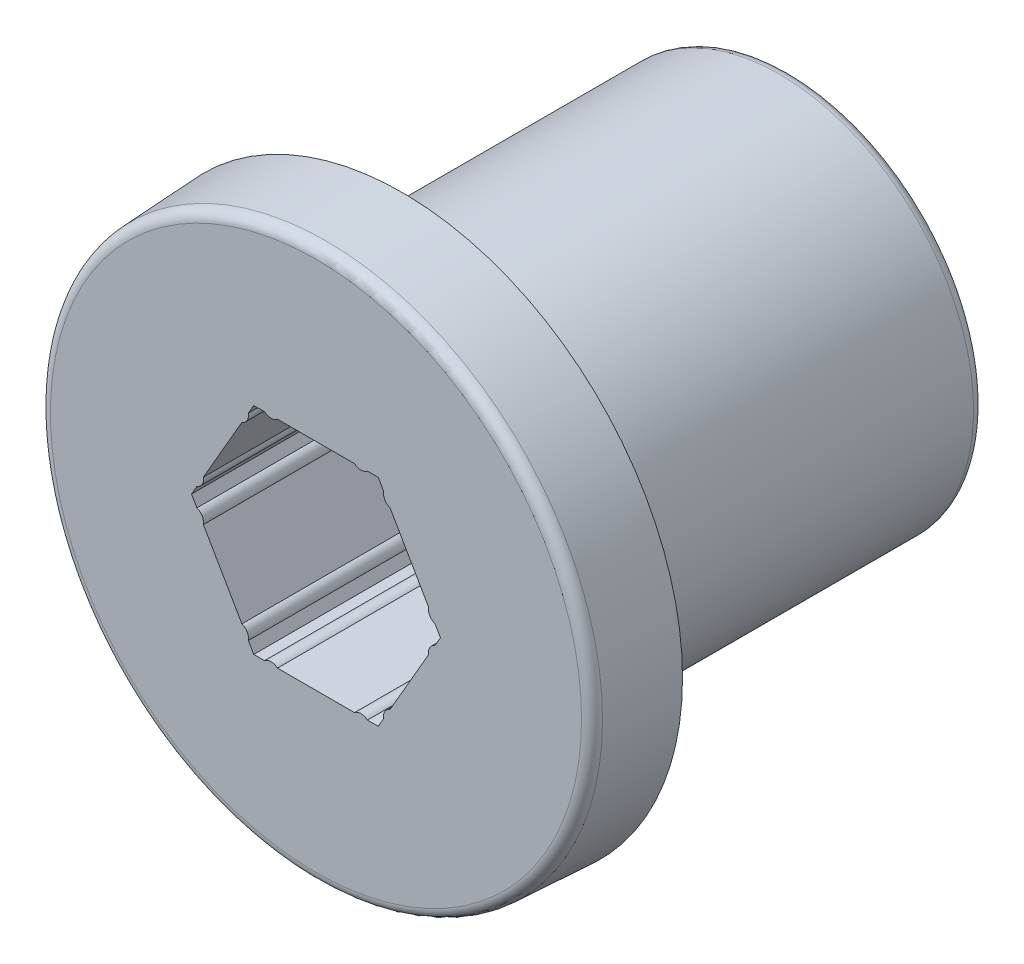
SolidWorks part; units mm, degrees
material "Rubber"
ref_plane "Front Plane" through (0, 0, 0) normal (0, 0, 1) x (1, 0, 0)
ref_plane "Top Plane" through (0, 0, 0) normal (0, 1, 0) x (1, 0, 0)
ref_plane "Right Plane" through (0, 0, 0) normal (1, 0, 0) x (0, 0, -1)
sketch "Sketch1" plane through (0, 0, 0) normal (0, 1, 0) x (1, 0, 0)
  line L0 (6.5, 0) -> (0, 0)
  line L1 (0, 0) -> (0, -2)
  line L2 (0, -2) -> (6.3952, -2)
  line L3 (6.3952, -2) -> (6.5, 0)
  line L4 (0, 0) -> (0, -2) construction
revolve "Revolve1" add sketch "Sketch1" angle 360 about L4 reverse direction yes
sketch "Sketch2" plane through (0, 0, 0) normal (0, 0, -1) x (-1, 0, 0)
  circle A0 centre (0, 0) radius 4.5
extrude "Boss-Extrude1" add sketch "Sketch2" along normal blind 9
sketch "Sketch3" plane through (0, 0, -9) normal (0, 0, -1) x (-1, 0, 0)
  line L0 (1.1934, -2.5) -> (1.4434, -2.5)
  line L1 (1.4434, -2.5) -> (1.5684, -2.2835)
  line L2 (1.7184, -2.0237) -> (2.6118, -0.4763)
  line L3 (2.7618, -0.2165) -> (2.8868, 0)
  line L4 (2.8868, 0) -> (2.7618, 0.2165)
  line L5 (2.6118, 0.4763) -> (1.7184, 2.0237)
  line L6 (1.5684, 2.2835) -> (1.4434, 2.5)
  line L7 (1.4434, 2.5) -> (1.1934, 2.5)
  line L8 (0.8934, 2.5) -> (-0.8934, 2.5)
  line L9 (-1.1934, 2.5) -> (-1.4434, 2.5)
  line L10 (-1.4434, 2.5) -> (-1.5684, 2.2835)
  line L11 (-1.7184, 2.0237) -> (-2.6118, 0.4763)
  line L12 (-2.7618, 0.2165) -> (-2.8868, 0)
  line L13 (-2.8868, 0) -> (-2.7618, -0.2165)
  line L14 (-2.6118, -0.4763) -> (-1.7184, -2.0237)
  line L15 (-1.5684, -2.2835) -> (-1.4434, -2.5)
  line L16 (-1.4434, -2.5) -> (-1.1934, -2.5)
  line L17 (-0.8934, -2.5) -> (0.8934, -2.5)
  arc A0 (0.8934, -2.5) -> (1.1934, -2.5) centre (1.0434, -2.677) cw
  arc A1 (1.5684, -2.2835) -> (1.7184, -2.0237) centre (1.7967, -2.2421) cw
  arc A2 (2.6118, -0.4763) -> (2.7618, -0.2165) centre (2.8401, -0.4349) cw
  arc A3 (2.7618, 0.2165) -> (2.6118, 0.4763) centre (2.8401, 0.4349) cw
  arc A4 (1.7184, 2.0237) -> (1.5684, 2.2835) centre (1.7967, 2.2421) cw
  arc A5 (1.1934, 2.5) -> (0.8934, 2.5) centre (1.0434, 2.677) cw
  arc A6 (-0.8934, 2.5) -> (-1.1934, 2.5) centre (-1.0434, 2.677) cw
  arc A7 (-1.5684, 2.2835) -> (-1.7184, 2.0237) centre (-1.7967, 2.2421) cw
  arc A8 (-2.6118, 0.4763) -> (-2.7618, 0.2165) centre (-2.8401, 0.4349) cw
  arc A9 (-2.7618, -0.2165) -> (-2.6118, -0.4763) centre (-2.8401, -0.4349) cw
  arc A10 (-1.7184, -2.0237) -> (-1.5684, -2.2835) centre (-1.7967, -2.2421) cw
  arc A11 (-1.1934, -2.5) -> (-0.8934, -2.5) centre (-1.0434, -2.677) cw
extrude "Cut-Extrude1" cut sketch "Sketch3" against normal through all
fillet "Fillet1" radius 0.25 2 edges at (0, 4.5, -9) (6.3952, 0, 2) tangent propagation no
